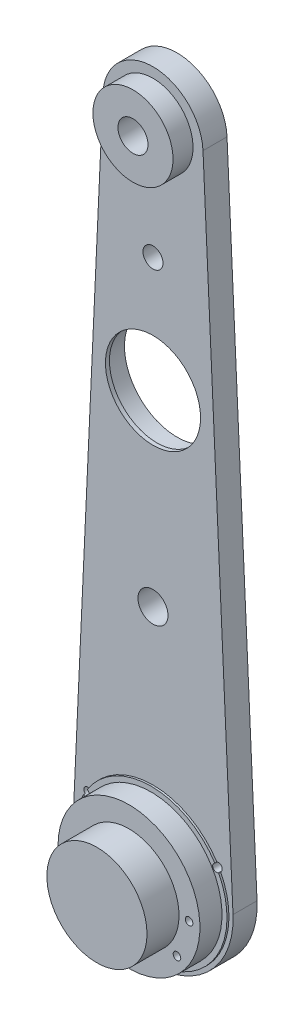
SolidWorks part; units mm, degrees
ref_plane "Front Plane" through (0, 0, 0) normal (0, 0, 1) x (1, 0, 0)
ref_plane "Top Plane" through (0, 0, 0) normal (0, 1, 0) x (1, 0, 0)
ref_plane "Right Plane" through (0, 0, 0) normal (1, 0, 0) x (0, 0, -1)
sketch "Sketch1" plane through (0, 0, 0) normal (0, 0, 1) x (1, 0, 0)
  line L0 (0, 205.4835) -> (0, 0) construction
  line L1 (25.3727, 1.1774) -> (15.8579, 206.2193)
  line L2 (-15.8579, 206.2193) -> (-25.3727, 1.1774)
  circle A1 centre (0, 205.4835) radius 4.7625
  arc A2 (-15.8579, 206.2193) -> (15.8579, 206.2193) centre (0, 205.4835) cw
  arc A3 (-25.3727, 1.1774) -> (25.3727, 1.1774) centre (0, 0) ccw
  dimension "D2" = 15.875
  dimension "D3" = 25.4
  dimension "D4" = 9.525
  dimension "D1" = 205.4835
extrude "Boss-Extrude1" add sketch "Sketch1" along normal mid plane 7.62
sketch "Sketch2" plane through (0, 0, 3.81) normal (0, 0, 1) x (1, 0, 0)
  circle A0 centre (0, 0) radius 22.5
  dimension "D1" = 45
extrude "Boss-Extrude2" add sketch "Sketch2" along normal blind 7.62
sketch "Sketch3" plane through (0, 0, 3.81) normal (0, 0, 1) x (1, 0, 0)
  circle A0 centre (0, 0) radius 24.0899
extrude "Boss-Extrude3" add sketch "Sketch3" along normal offset from surface (0.62 mm away) 7 up to face at (22.5, 0, 11.43)
sketch "Sketch4" plane through (0, 0, 3.81) normal (0, 0, 1) x (1, 0, 0)
  circle A0 centre (0, 73.0199) radius 4.7625
  circle A1 centre (0, 132.4635) radius 16.6688
  circle A2 centre (0, 205.4835) radius 4.7625 construction
  dimension "D2" = 9.525
  dimension "D3" = 33.3375
  dimension "D1" = 73.0199
  dimension "D4" = 73.0199
extrude "Cut-Extrude1" cut sketch "Sketch4" against normal through all both and the other way through all
sketch "Sketch5" plane through (0, 0, 0) normal (0, 0, 1) x (1, 0, 0)
  line L0 (-155.5635, 72.3706) -> (0, 227.9341)
  line L1 (-155.5635, 72.3706) -> (0, -83.1929)
  line L2 (0, 227.9341) -> (155.5635, 72.3706)
  line L3 (0, -83.1929) -> (155.5635, 72.3706)
  line L4 (-155.5635, 72.3706) -> (155.5635, 72.3706) construction
  line L5 (0, 227.9341) -> (0, -83.1929) construction
  arc A1 (15.8579, 206.2193) -> (-15.8579, 206.2193) centre (0, 205.4835) ccw construction
  point P1 (0, 72.3706)
  dimension "D1" = 220
sketch "Sketch6" plane through (0, 0, 3.81) normal (0, 0, 1) x (1, 0, 0)
  circle A0 centre (0, 132.4635) radius 16.6688
  circle A1 centre (0, 132.4635) radius 15.0813
  circle A2 centre (0, 132.4635) radius 16.6688 construction
  dimension "D1" = 1.5875
extrude "Boss-Extrude4" add sketch "Sketch6" against normal offset from surface (1.27 mm away) 6.35 up to face at (4.7625, 73.0199, -3.81)
sketch "Sketch7" plane through (0, 0, -3.81) normal (0, 0, -1) x (-1, 0, 0)
  line L0 (11, -20.6542) -> (11, 7.5625) construction
  line L1 (-11.7938, -25.4) -> (11.7937, -25.4)
  line L2 (-11.7938, -25.4) -> (-11.7938, 8.3563)
  line L3 (-11.7938, 8.3563) -> (11.7937, 8.3563)
  line L4 (11.7937, -25.4) -> (11.7937, 8.3563)
  line L5 (-11.7938, -25.4) -> (11.7937, 8.3563) construction
  line L6 (-11.7938, 8.3563) -> (11.7937, -25.4) construction
  line L7 (11, 7.5625) -> (-11, 7.5625) construction
  arc A0 (-25.3727, 1.1774) -> (25.3727, 1.1774) centre (0, 0) ccw construction
  point P0 (0, -8.5219)
  dimension "D1" = 0.7937
  dimension "D2" = 0.7937
extrude "Cut-Extrude2" cut sketch "Sketch7" against normal blind 1.5875
sketch "Sketch8" plane through (0, 0, -2.2225) normal (0, 0, -1) x (-1, 0, 0)
  circle A0 centre (-9, 5.5625) radius 0.95
  circle A1 centre (9, 5.5625) radius 0.95
  circle A2 centre (9, -5.5625) radius 0.95
  circle A3 centre (-9, -5.5625) radius 0.95
  dimension "D1" = 1.9
extrude "Cut-Extrude3" cut sketch "Sketch8" against normal through all
sketch "Sketch9" plane through (0, 0, 3.81) normal (0, 0, 1) x (1, 0, 0)
  circle A0 centre (0, 205.4835) radius 12.7
  circle A1 centre (0, 205.4835) radius 4.7625 construction
  circle A2 centre (0, 205.4835) radius 4.7625
  dimension "D1" = 25.4
extrude "Boss-Extrude5" add sketch "Sketch9" along normal blind 6.35
sketch "Sketch10" plane through (0, 0, 11.43) normal (0, 0, 1) x (1, 0, 0)
  circle A0 centre (0, 0) radius 15.875
  dimension "D1" = 31.75
extrude "Boss-Extrude6" add sketch "Sketch10" along normal blind 10.16
sketch "Sketch11" plane through (0, 0, -3.81) normal (0, 0, -1) x (-1, 0, 0)
  circle A0 centre (-20.7431, 11.983) radius 1.2
  circle A1 centre (20.7431, 11.983) radius 1.2
  circle A2 centre (19.0618, 0) radius 1.2
  circle A3 centre (15.2212, -11.4747) radius 1.2
  circle A4 centre (-15.2212, -11.4747) radius 1.2
  circle A5 centre (-19.0618, 0) radius 1.2
  dimension "D1" = 2.4
extrude "Cut-Extrude4" cut sketch "Sketch11" against normal through all both and the other way through all
sketch "Sketch12" plane through (0, 0, 3.81) normal (0, 0, 1) x (1, 0, 0)
  line L3 (0, 132.4635) -> (0, 205.4835) construction
  circle A7 centre (0, 132.4635) radius 15.0813 construction
  circle A8 centre (0, 205.4835) radius 4.7625 construction
  circle A9 centre (0, 168.9735) radius 3.175
  dimension "D1" = 6.35
extrude "Cut-Extrude5" cut sketch "Sketch12" against normal through all
equation "\"UpperLinkLength\"= \"LowerFirstStage\" + \"LowerSecondStage\""
equation "\"LowerFirstStage\"= \"60T_20T_171B\""
equation "\"LowerSecondStage\"= \"60T_20T_113B\""
equation "\"D1@Sketch1\"=\"UpperLinkLength\""
equation "\"UpperStage\"= \"60T_20T_113B\""
equation "\"60T_20T_113B\"= 2.8748"
equation "\"60T_20T_171B\"= 5.2151"
equation "\"D1@Sketch4\"=\"UpperStage\""
equation "\"D4@Sketch4\"=\"LowerSecondStage\""
